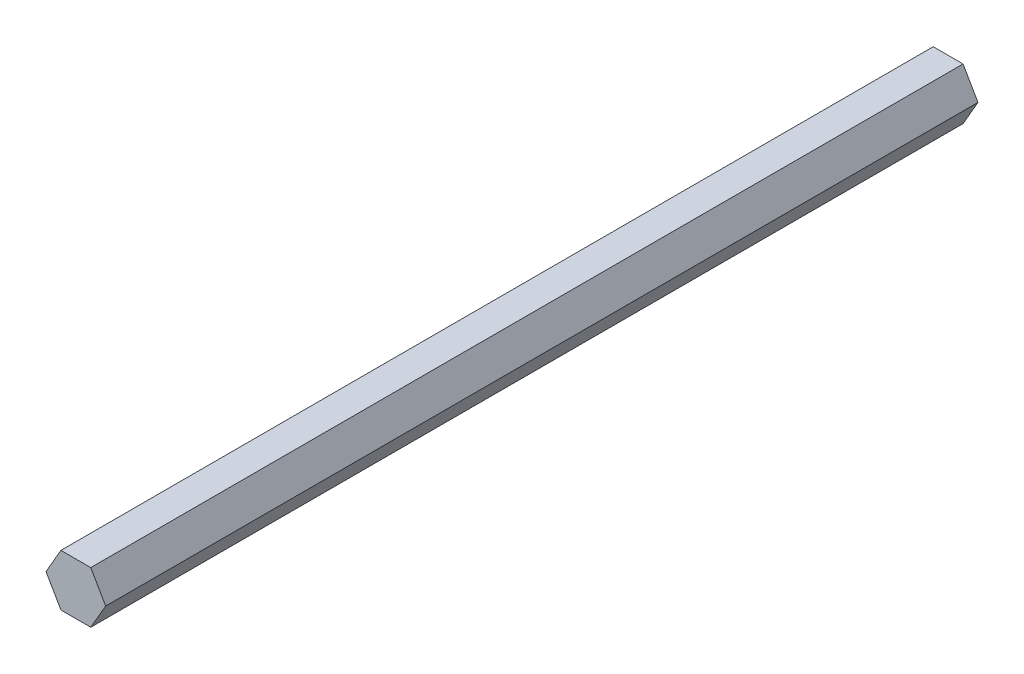
SolidWorks part; units mm, degrees
ref_plane "Front Plane" through (0, 0, 0) normal (0, 0, 1) x (1, 0, 0)
ref_plane "Top Plane" through (0, 0, 0) normal (0, 1, 0) x (1, 0, 0)
ref_plane "Right Plane" through (0, 0, 0) normal (1, 0, 0) x (0, 0, -1)
sketch "Sketch1" plane through (0, 0, 0) normal (0, 0, 1) x (1, 0, 0)
  line L1 (-7.3323, 0) -> (-3.6662, -6.35)
  line L2 (-3.6662, -6.35) -> (3.6662, -6.35)
  line L3 (3.6662, -6.35) -> (7.3323, 0)
  line L4 (7.3323, 0) -> (3.6662, 6.35)
  line L5 (3.6662, 6.35) -> (-3.6662, 6.35)
  line L6 (-3.6662, 6.35) -> (-7.3323, 0)
  circle A0 centre (0, 0) radius 6.35 construction
  dimension "D1" = 12.7
extrude "Boss-Extrude1" add sketch "Sketch1" along normal blind 214.3125
